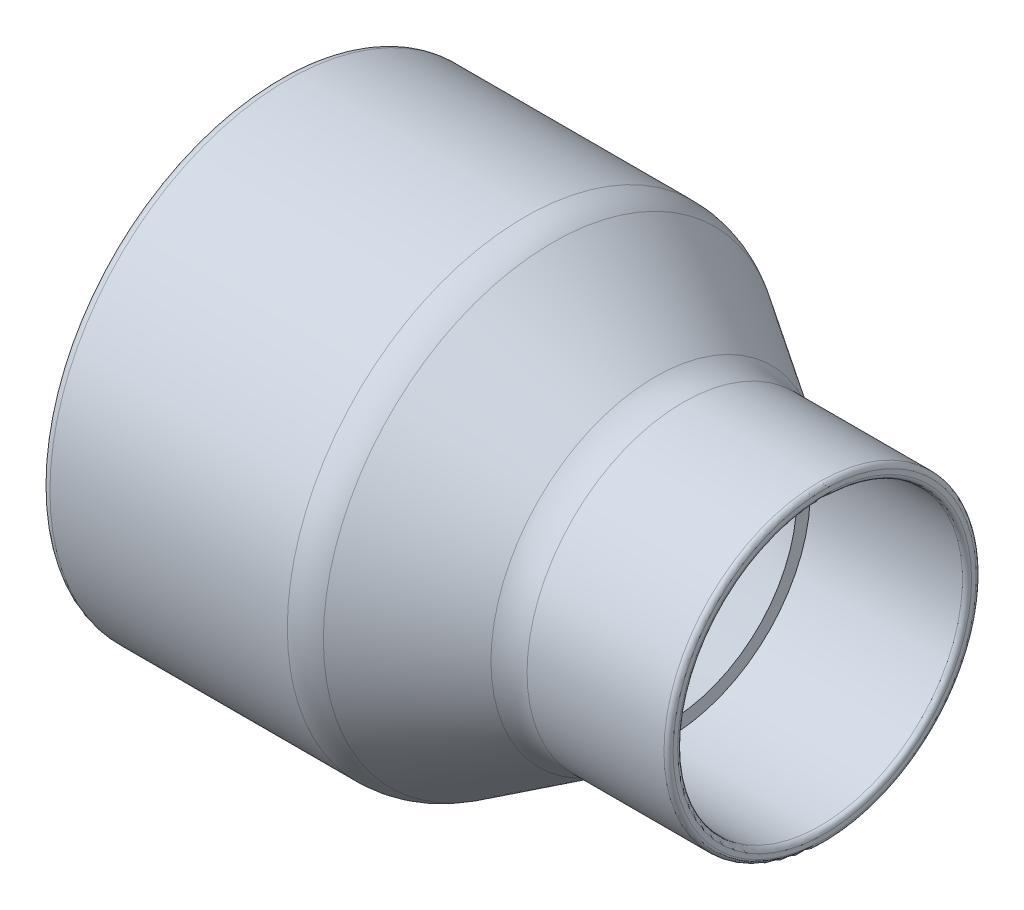
SolidWorks part; units mm, degrees
material "PE Высокой плотности"
ref_plane "Спереди" through (0, 0, 0) normal (0, 0, 1) x (1, 0, 0)
ref_plane "Сверху" through (0, 0, 0) normal (0, 1, 0) x (1, 0, 0)
ref_plane "Справа" through (0, 0, 0) normal (1, 0, 0) x (0, 0, -1)
sketch "Эскиз1" plane through (0, 0, 0) normal (0, 0, 1) x (1, 0, 0)
  line L0 (-72, 0) -> (72, 0) construction
  line L1 (-72, 60) -> (-72, 57.5)
  line L2 (-69.5, 55) -> (-4.2, 55)
  line L3 (-3, 55) -> (30.75, 37.5) construction
  line L4 (30.75, 37.5) -> (70.8, 37.5)
  line L5 (72, 38.7) -> (72, 39.9)
  line L6 (70.8, 41.1) -> (34.7418, 41.1)
  line L7 (27.3787, 43.2376) -> (0.3713, 60.3624)
  line L8 (-6.9918, 62.5) -> (-69.5, 62.5)
  line L9 (-3, 62.5) -> (-3, 60.7103) construction
  line L10 (-3, 51.4) -> (30.75, 33.9)
  line L11 (-3, 51.4) -> (-3, 53.8)
  line L12 (30.75, 33.9) -> (30.75, 37.5)
  line L13 (30.75, 33.9) -> (62.4318, 33.9) construction
  arc A0 (-72, 57.5) -> (-69.5, 55) centre (-69.5, 57.5) ccw
  arc A1 (-69.5, 62.5) -> (-72, 60) centre (-69.5, 60) ccw
  arc A2 (70.8, 37.5) -> (72, 38.7) centre (70.8, 38.7) ccw
  arc A3 (72, 39.9) -> (70.8, 41.1) centre (70.8, 39.9) ccw
  arc A4 (0.3713, 60.3624) -> (-6.9918, 62.5) centre (-6.9918, 48.75) ccw
  arc A5 (34.7418, 41.1) -> (27.3787, 43.2376) centre (34.7418, 54.85) cw
  arc A6 (-4.2, 55) -> (-3, 53.8) centre (-4.2, 53.8) cw
  point P2 (-72, 62.5)
  point P13 (72, 33.9)
  point P15 (-72, 49.7)
  point P24 (-72, 62.5)
  point P29 (72, 41.1)
  point P36 (30.75, 41.1)
  point P40 (30.75, 0)
  point P41 (-3, 0)
  dimension "D4" = 144
  dimension "D3" = 41.25
  dimension "D7" = 2.5
  dimension "D8" = 1.2
  dimension "D9" = 13.75
  dimension "D10" = 13.75
  dimension "D11" = 1.2
  dimension "D5" = 69
  dimension "D6" = 3.6
  dimension "D1вну/2" = 62.5
  dimension "D1нар/2" = 62.5
  dimension "D2нар/2" = 55
  dimension "D2вну/2" = 49.7
  dimension "d_нар/2" = 37.5
  dimension "d_вну/2" = 33.9
revolve "Повернуть1" add sketch "Эскиз1" angle 360 about L0
other "Точка соединения1" parameters "Диаметр"=110, "StubLength"=0
ref_axis "Ось1" through (-13, 0, 0) along (1, 0, 0)
other "Точка соединения2" parameters "Диаметр"=75, "StubLength"=0
ref_axis "Ось2" through (40.75, 0, 0) along (-1, 0, 0)
other "Точка маршрута1"
equation "\"D3@Эскиз1\"=1.1*\"d_нар/2@Эскиз1\""
equation "\"D6@Эскиз1\" = \"d_нар/2@Эскиз1\" - \"d_вну/2@Эскиз1\""
equation "\"D7@Эскиз1\" = ( \"D1вну/2@Эскиз1\" - \"D2нар/2@Эскиз1\" ) / 3"
equation "\"D8@Эскиз1\" = \"D6@Эскиз1\" / 3"
equation "\"D9@Эскиз1\" = \"D3@Эскиз1\" / 3"
equation "\"D10@Эскиз1\"=\"D9@Эскиз1\""
equation "\"D11@Эскиз1\"=\"D8@Эскиз1\""
